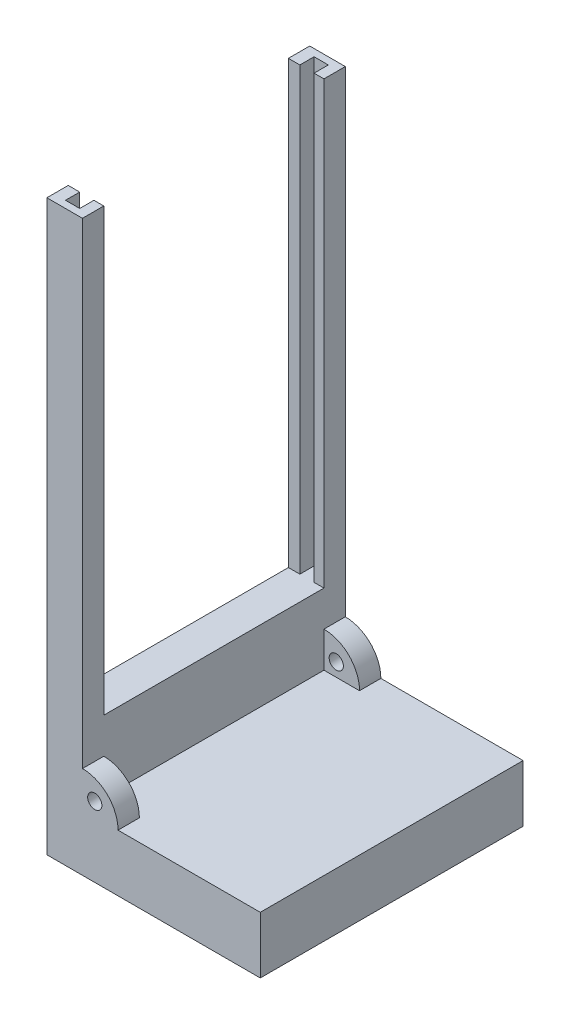
SolidWorks part; units mm, degrees
ref_plane "Front Plane" through (0, 0, 0) normal (0, 0, 1) x (1, 0, 0)
ref_plane "Top Plane" through (0, 0, 0) normal (0, 1, 0) x (1, 0, 0)
ref_plane "Right Plane" through (0, 0, 0) normal (1, 0, 0) x (0, 0, -1)
sketch "Sketch1" plane through (0, 0, 0) normal (1, 0, 0) x (0, 0, -1)
  line L1 (-184.7575, 400) -> (184.7575, 400)
  line L2 (-184.7575, 400) -> (-184.7575, -400)
  line L3 (-184.7575, -400) -> (184.7575, -400)
  line L4 (184.7575, 400) -> (184.7575, -400)
  line L5 (-184.7575, 400) -> (184.7575, -400) construction
  line L6 (-184.7575, -400) -> (184.7575, 400) construction
  point P0 (0, 0)
  dimension "D1" = 800
extrude "Boss-Extrude1" add sketch "Sketch1" along normal blind 80
sketch "Sketch2" plane through (80, 0, 0) normal (1, 0, 0) x (0, 0, -1)
  line L0 (184.7575, -400) -> (184.7575, 400) construction
  line L1 (-184.7575, -400) -> (184.7575, -400)
  line L2 (-184.7575, -400) -> (-184.7575, -320)
  line L3 (-184.7575, -320) -> (184.7575, -320)
  line L4 (184.7575, -400) -> (184.7575, -320)
  dimension "D1" = 80
extrude "Boss-Extrude2" add sketch "Sketch2" along normal blind 250
sketch "Sketch3" plane through (0, 0, -184.7575) normal (0, 0, -1) x (-1, 0, 0)
  line L1 (-80, -320) -> (-130, -320)
  line L2 (-80, -320) -> (-80, -270)
  line L3 (-80, -270) -> (-130, -270)
  line L4 (-130, -320) -> (-130, -270)
  dimension "D1" = 50
  dimension "D2" = 50
extrude "Boss-Extrude3" add sketch "Sketch3" against normal blind 30
sketch "Sketch4" plane through (0, 0, 184.7575) normal (0, 0, 1) x (1, 0, 0)
  line L1 (80, -320) -> (130, -320)
  line L2 (80, -320) -> (80, -270)
  line L3 (80, -270) -> (130, -270)
  line L4 (130, -320) -> (130, -270)
extrude "Boss-Extrude4" add sketch "Sketch4" against normal blind 30
sketch "Sketch5" plane through (80, 0, 0) normal (1, 0, 0) x (0, 0, -1)
  line L0 (-184.7575, 400) -> (-184.7575, -270) construction
  line L1 (-154.7575, 430) -> (154.7575, 430)
  line L2 (-154.7575, 430) -> (-154.7575, -220)
  line L3 (-154.7575, -220) -> (154.7575, -220)
  line L4 (154.7575, 430) -> (154.7575, -220)
  line L5 (184.7575, -270) -> (184.7575, 400) construction
  line L6 (184.7575, -320) -> (-184.7575, -320) construction
  dimension "D1" = 650
  dimension "D2" = 30
  dimension "D3" = 30
  dimension "D4" = 100
extrude "Cut-Extrude1" cut sketch "Sketch5" against normal through all contours L1 L4 L3 L2
sketch "Sketch6" plane through (0, 0, 0) normal (-1, 0, 0) x (0, 0, 1)
  line L1 (-184.7575, 400) -> (184.7575, 400)
  line L2 (-184.7575, 400) -> (-184.7575, -400)
  line L3 (-184.7575, -400) -> (184.7575, -400)
  line L4 (184.7575, 400) -> (184.7575, -400)
extrude "Cut-Extrude2" cut sketch "Sketch6" against normal blind 30
sketch "Sketch7" plane through (0, 0, 154.7575) normal (0, 0, -1) x (-1, 0, 0)
  line L0 (-30, -220) -> (-80, -220) construction
  line L1 (-66.1338, 400) -> (-46.1338, 400)
  line L2 (-66.1338, 400) -> (-66.1338, -220)
  line L3 (-66.1338, -220) -> (-46.1338, -220)
  line L4 (-46.1338, 400) -> (-46.1338, -220)
  line L5 (-66.1338, 400) -> (-46.1338, -220) construction
  line L6 (-66.1338, -220) -> (-46.1338, 400) construction
  line L7 (-30, 400) -> (-30, -220) construction
  point P0 (-56.1338, 90)
  dimension "D1" = 20
extrude "Cut-Extrude3" cut sketch "Sketch7" against normal blind 20
mirror "Mirror1" about plane through (0, 0, 0) normal (0, 0, 1) of "Cut-Extrude3"
fillet "Fillet1" radius 50 2 edges at (130, -270, 169.7575) (130, -270, -169.7575)
sketch "Sketch8" plane through (0, 0, -184.7575) normal (0, 0, -1) x (-1, 0, 0)
  circle A0 centre (-97.3049, -301.216) radius 10
  dimension "D1" = 20
extrude "Cut-Extrude4" cut sketch "Sketch8" against normal through all
sketch "Sketch9" plane through (30, 0, 0) normal (-1, 0, 0) x (0, 0, 1)
  text T0 "Holder" font "Clarendon Blk BT" height in points 150
extrude "Cut-Extrude5" cut sketch "Sketch9" against normal blind 10
